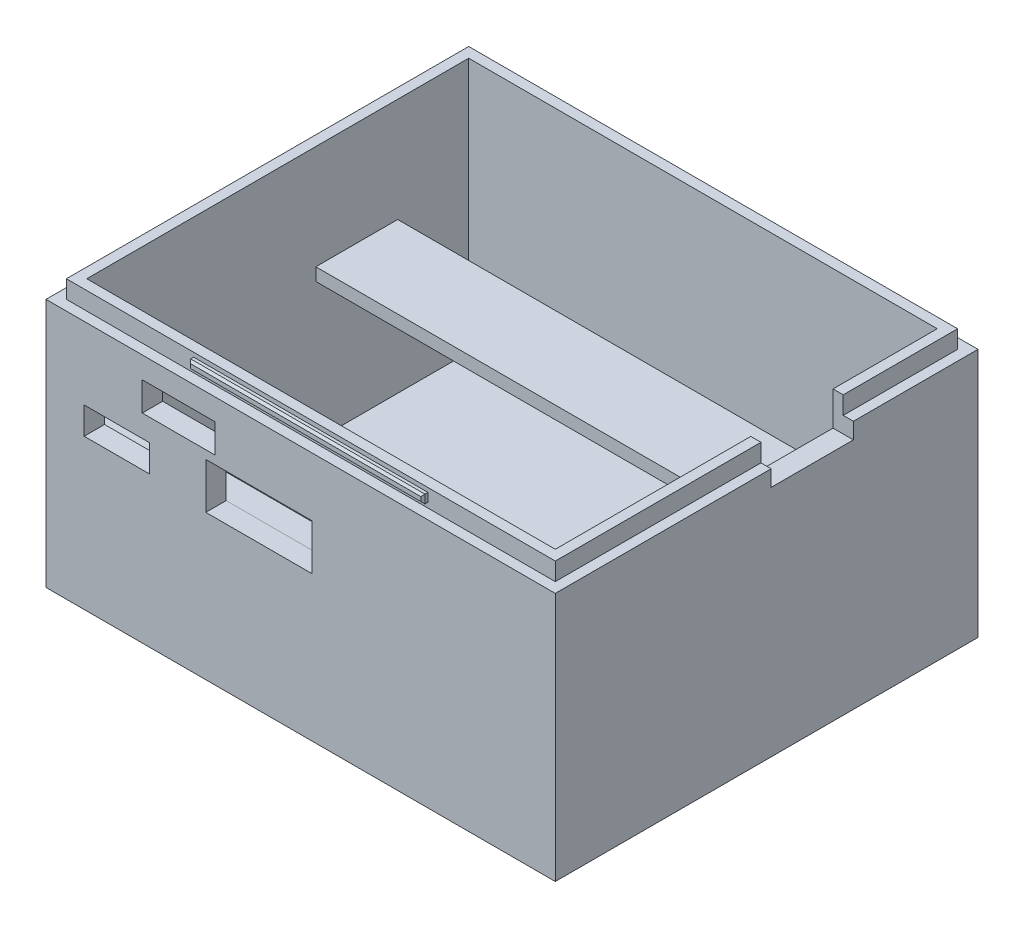
SolidWorks part; units mm, degrees
ref_plane "Front Plane" through (0, 0, 0) normal (0, 0, 1) x (1, 0, 0)
ref_plane "Top Plane" through (0, 0, 0) normal (0, 1, 0) x (1, 0, 0)
ref_plane "Right Plane" through (0, 0, 0) normal (1, 0, 0) x (0, 0, -1)
sketch "BatteryAndOuterWalls" plane through (0, 0, 0) normal (0, 1, 0) x (1, 0, 0)
  line L0 (30, -24.9) -> (30, 24.9)
  line L1 (27.6, -22.5) -> (-27.6, -22.5)
  line L2 (27.6, -22.5) -> (27.6, 22.5)
  line L3 (27.6, 22.5) -> (-27.6, 22.5)
  line L4 (-27.6, -22.5) -> (-27.6, 22.5)
  line L5 (27.6, -22.5) -> (-27.6, 22.5) construction
  line L6 (27.6, 22.5) -> (-27.6, -22.5) construction
  line L7 (30, 24.9) -> (-30, 24.9)
  line L8 (-30, -24.9) -> (-30, 24.9)
  line L9 (30, -24.9) -> (-30, -24.9)
  point P0 (0, 0)
  dimension "D1" = 55.2
  dimension "D2" = 45
  dimension "D4" = 60
  dimension "D5" = 49.8
  dimension "D3" = 2.4
extrude "Walls" add sketch "BatteryAndOuterWalls" along normal blind 30
sketch "SinkRim" plane through (0, 30, 0) normal (0, 1, 0) x (1, 0, 0)
  line L0 (-28.8, 23.7) -> (-28.8, -23.7)
  line L5 (-27.6, 22.5) -> (27.6, 22.5)
  line L6 (-27.6, 22.5) -> (-27.6, -22.5)
  line L7 (-27.6, -22.5) -> (27.6, -22.5)
  line L8 (27.6, 22.5) -> (27.6, -22.5)
  line L9 (-28.8, -23.7) -> (28.8, -23.7)
  line L10 (28.8, 23.7) -> (28.8, -23.7)
  line L11 (-28.8, 23.7) -> (28.8, 23.7)
  line L12 (-30, 24.9) -> (30, 24.9)
  line L13 (30, 24.9) -> (30, -24.9)
  line L14 (-30, -24.9) -> (30, -24.9)
  line L15 (-30, 24.9) -> (-30, -24.9)
  line M5 (-30, -24.9) -> (30, -24.9)
  line M6 (30, -24.9) -> (30, 24.9)
  line M7 (30, 24.9) -> (-30, 24.9)
  line M8 (-30, 24.9) -> (-30, -24.9)
  dimension "D1" = 1.2
  dimension "D2" = 1.2
sketch "Sketch2" plane through (0, 0, 0) normal (0, -1, 0) x (1, 0, 0)
  line L0 (-30, 24.9) -> (30, 24.9) construction
  line L5 (-30, 24.9) -> (30, 24.9)
  line L6 (-30, 24.9) -> (-30, -24.9)
  line L7 (-30, -24.9) -> (30, -24.9)
  line L8 (30, 24.9) -> (30, -24.9)
  line L9 (-30, -24.9) -> (-30, 24.9) construction
extrude "Bottom" add sketch "Sketch2" along normal blind 1.5
extrude "Top-Cut" cut sketch "SinkRim" against normal blind 2.1 contours L0 L11 L10 L9 M8 M5 M6 M7 region at (0, 30, -24.1203)
sketch "FrontRail" plane through (30, 0, 0) normal (1, 0, 0) x (0, 0, -1)
  line L0 (13.6255, 20.7301) -> (-12.2825, 20.7301) construction
  line L1 (-22.5132, 30) -> (22.5, 30)
  line L3 (-22.5132, 0) -> (22.5, 0)
  line L4 (22.5, 30) -> (22.5, 0)
  line L5 (24.9, -1.5) -> (-24.9, -1.5) construction
  line L6 (24.9, 27.9) -> (24.9, -1.5) construction
  line L7 (23.7, 30) -> (-23.7, 30) construction
  line L8 (-22.5132, 0) -> (-22.5132, 30)
  line L31 (-22.5132, 14) -> (-19.5132, 14)
  line L36 (-22.5132, 14) -> (-22.5132, 15.5)
  line L37 (-22.5132, 15.5) -> (-19.5132, 15.5)
  line L38 (-19.5132, 14) -> (-19.5132, 15.5)
  line L39 (-4.5132, 17.7301) -> (22.5, 17.7301)
  line L40 (-4.5132, 17.7301) -> (-4.5132, 16.2301)
  line L41 (-4.5132, 16.2301) -> (22.5, 16.2301)
  line L42 (22.5, 17.7301) -> (22.5, 16.2301)
  dimension "D10" = 0
  dimension "D6" = 3
  dimension "D1" = 14
  dimension "D2" = 1.5
  dimension "D3" = 2.4
  dimension "D4" = 0
  dimension "D5" = 1.5
  dimension "D7" = 1.5
  dimension "D8" = 3
  dimension "D9" = 15
extrude "PCB-Supports" add sketch "FrontRail" against normal blind 60 contours L41 L42 L39 L40 | L37 L38 L31 L36
sketch "Sketch3" plane through (0, 0, 0) normal (0, 1, 0) x (1, 0, 0)
  line L1 (-27.6, 22.5) -> (27.6, 22.5)
  line L2 (-27.6, 22.5) -> (-27.6, -22.5)
  line L3 (-27.6, -22.5) -> (27.6, -22.5)
  line L4 (27.6, 22.5) -> (27.6, -22.5)
  line L5 (27.6, 22.5) -> (-27.6, 22.5)
  line L6 (27.6, 22.5) -> (27.6, 14.1305)
  line L7 (27.6, 14.1305) -> (-27.6, 14.1305)
  line L8 (-27.6, 22.5) -> (-27.6, 14.1305)
  line L9 (-27.6, -4.5132) -> (27.6, -4.5132)
  line L10 (-27.6, -4.5132) -> (-27.6, 4.4868)
  line L11 (-27.6, 4.4868) -> (27.6, 4.4868)
  line L12 (27.6, -4.5132) -> (27.6, 4.4868)
  dimension "D1" = 9
  dimension "D2" = 8.3695
extrude "Battery-Insertion-Cut" cut sketch "Sketch3" along normal blind 25 contours L7 L4 L1 L2 | L11 L12 L9 L10 region at (0, 0, -18.3153)
sketch "USB_FRONT" plane through (0, 0, 24.9) normal (0, 0, 1) x (1, 0, 0)
  line L1 (-25.5021, 16.1801) -> (-17.8193, 16.1801)
  line L2 (-25.5021, 16.1801) -> (-25.5021, 19.3701)
  line L3 (-25.5021, 19.3701) -> (-17.8193, 19.3701)
  line L4 (-17.8193, 16.1801) -> (-17.8193, 19.3701)
  line L5 (-11.1723, 15.5801) -> (-11.1723, 20.9801)
  line L10 (-11.1723, 20.9801) -> (1.3277, 20.9801)
  line L11 (1.3277, 15.5801) -> (1.3277, 20.9801)
  line L12 (-11.1723, 15.5801) -> (1.3277, 15.5801)
  line L14 (-18.6623, 21.9683) -> (-10.0919, 21.9683)
  line L15 (-18.6623, 21.9683) -> (-18.6623, 25.3647)
  line L16 (-18.6623, 25.3647) -> (-10.0919, 25.3647)
  line L17 (-10.0919, 21.9683) -> (-10.0919, 25.3647)
extrude "USB-Front-Cut" cut sketch "USB_FRONT" against normal blind 10
sketch "USB-Right-Sketch" plane through (30, 0, 0) normal (1, 0, 0) x (0, 0, -1)
  line L1 (0.5301, 30) -> (10.2205, 30)
  line L2 (0.5301, 30) -> (0.5301, 26)
  line L3 (0.5301, 26) -> (10.2205, 26)
  line L4 (10.2205, 30) -> (10.2205, 26)
  line L5 (23.7, 30) -> (-23.7, 30) construction
  dimension "D1" = 0
  dimension "D2" = 4
extrude "Cut-Extrude3" cut sketch "USB-Right-Sketch" against normal blind 5
ref_plane "Plane1" through (0, 0, 0) normal (0, 0, 1) x (1, 0, 0)
sketch "Sketch7" plane through (0, 0, 23.7) normal (0, 0, 1) x (1, 0, 0)
  line L0 (-28.8, 30) -> (28.8, 30) construction
  line L1 (-13.8, 29.5) -> (13.8, 29.5)
  line L2 (-13.8, 29.5) -> (-13.8, 28.5)
  line L3 (-13.8, 28.5) -> (13.8, 28.5)
  line L4 (13.8, 29.5) -> (13.8, 28.5)
  line L5 (-30, 27.9) -> (30, 27.9) construction
  line L6 (-28.8, 27.9) -> (-28.8, 30) construction
  line L7 (28.8, 27.9) -> (28.8, 30) construction
  dimension "D1" = 0.5
  dimension "D2" = 1
  dimension "D3" = 0.6
  dimension "D4" = 15
  dimension "D5" = 15
extrude "Lid-Ridge-Front" add sketch "Sketch7" along normal blind 0.6
chamfer "Lid-Ridge-Front-Chamfer" distance 0.25 angle 45 4 edges at (0, 29.5, 24.3) (13.8, 29, 24.3) (0, 28.5, 24.3) (-13.8, 29, 24.3)
mirror "Mirror1" about plane through (0, 0, 0) normal (0, 0, 1) of "Lid-Ridge-Front-Chamfer", "Lid-Ridge-Front"
fillet "Fillet1" [suppressed] radius 2
